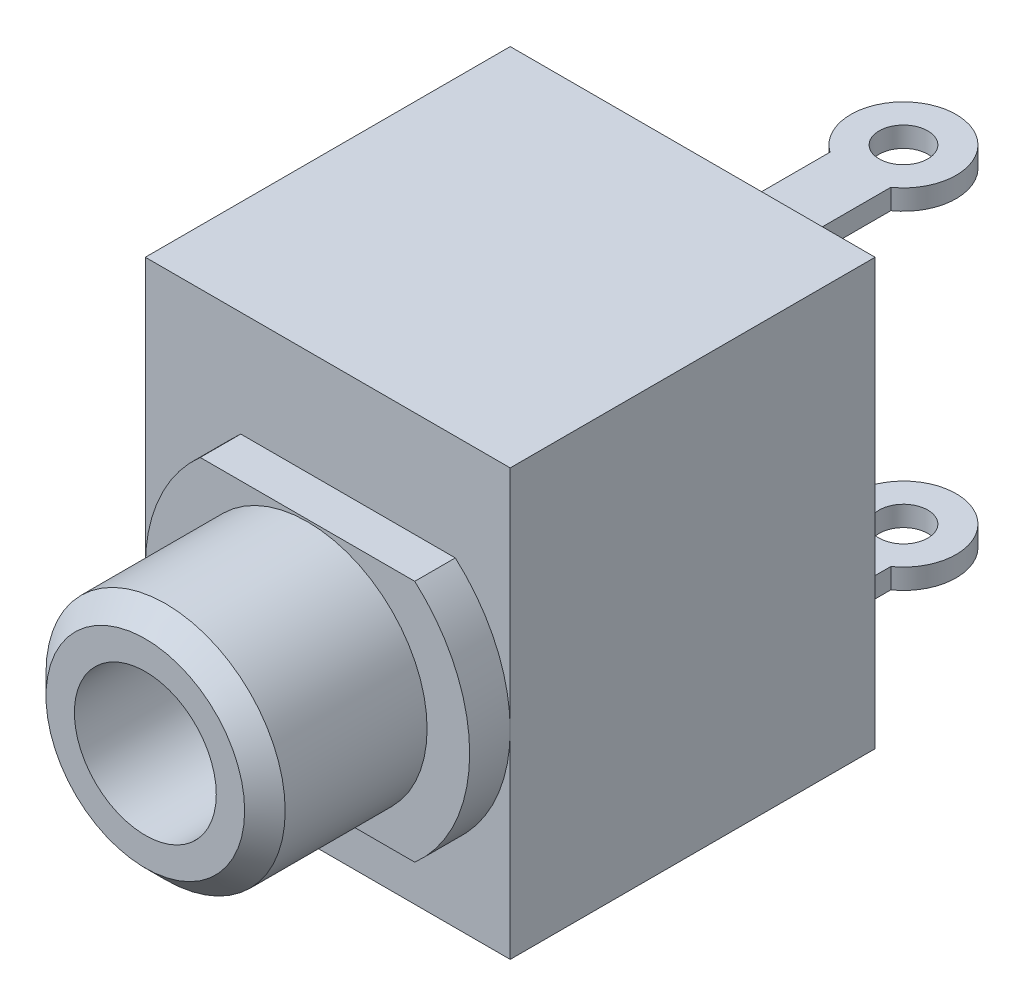
SolidWorks part; units mm, degrees
ref_plane "Front" through (0, 0, 0) normal (0, 0, 1) x (1, 0, 0)
ref_plane "Top" through (0, 0, 0) normal (0, 1, 0) x (1, 0, 0)
ref_plane "Right" through (0, 0, 0) normal (1, 0, 0) x (0, 0, -1)
sketch "Sketch3" plane through (0, 0, 0) normal (0, 0, 1) x (1, 0, 0)
  line L0 (1, -3.7) -> (1, 4.4) construction
  line L1 (-5, 5.6) -> (4, 5.6)
  line L2 (-5, 5.6) -> (-5, -4.9)
  line L3 (-5, -4.9) -> (4, -4.9)
  line L4 (4, 5.6) -> (4, -4.9)
  line L5 (0.25, -3.45) -> (1.75, -3.45)
  line L6 (0.25, -3.45) -> (0.25, -3.95)
  line L7 (0.25, -3.95) -> (1.75, -3.95)
  line L8 (1.75, -3.45) -> (1.75, -3.95)
  line L9 (0.25, -3.45) -> (1.75, -3.95) construction
  line L10 (0.25, -3.95) -> (1.75, -3.45) construction
  line L11 (-4.05, -0.65) -> (-3.55, -0.65)
  line L12 (-4.05, -0.65) -> (-4.05, -2.15)
  line L13 (-4.05, -2.15) -> (-3.55, -2.15)
  line L14 (-3.55, -0.65) -> (-3.55, -2.15)
  line L15 (-4.05, -0.65) -> (-3.55, -2.15) construction
  line L16 (-4.05, -2.15) -> (-3.55, -0.65) construction
  line L17 (0.25, 4.65) -> (1.75, 4.65)
  line L18 (0.25, 4.65) -> (0.25, 4.15)
  line L19 (0.25, 4.15) -> (1.75, 4.15)
  line L20 (1.75, 4.65) -> (1.75, 4.15)
  line L21 (0.25, 4.65) -> (1.75, 4.15) construction
  line L22 (0.25, 4.15) -> (1.75, 4.65) construction
  point P4 (1, -3.7)
  point P10 (-3.8, -1.4)
  point P15 (1, 4.4)
  dimension "D1" = 9
  dimension "D2" = 10.5
  dimension "D3" = 4
  dimension "D4" = 4.9
  dimension "D5" = 0.5
  dimension "D6" = 1.5
  dimension "D7" = 1
  dimension "D8" = 3.7
  dimension "D9" = 4.4
  dimension "D10" = 3.8
  dimension "D11" = 1.4
extrude "Boss-Extrude1" add sketch "Sketch3" along normal blind 9 contours L20 L17 L18 L19 | L14 L11 L12 L13 | L8 L5 L6 L7 | L4 L1 L2 L3 L5 L8 L7 L6 L11 L14 L13 L12 L17 L20 L19 L18 region at (-0.4976, 0.3642, 0) region at (1, -3.7, 0) region at (-3.8, -1.4, 0) region at (1, 4.4, 0)
sketch "Sketch5" plane through (0, 0, 9) normal (0, 0, 1) x (1, 0, 0)
  line L0 (4, 5.6) -> (4, -4.9) construction
  line L1 (-4, -3) -> (4, -3)
  line L2 (-4, -3) -> (-4, 3)
  line L3 (-4, 3) -> (4, 3)
  line L4 (4, -3) -> (4, 3)
  line L5 (-4, -3) -> (4, 3) construction
  line L6 (-4, 3) -> (4, -3) construction
  circle A0 centre (0, 0) radius 1.75
  circle A1 centre (0, 0) radius 2.95
  circle A2 centre (0, 0) radius 4
  dimension "D2" = 5.9
  dimension "D3" = 3.5
  dimension "D1" = 6
extrude "Boss-Extrude4" add sketch "Sketch5" along normal blind 1 contours L3 A2 L1 A1 region at (-3.5546, -1.6046, 9)
extrude "Boss-Extrude5" add sketch "Sketch5<3>" along normal blind 5 contours A1 A0 region at (-2.8666, 0, 9)
sketch "Sketch5<3>" plane through (0, 0, 9) normal (0, 0, 1) x (1, 0, 0) same geometry as "Sketch5"
extrude "Boss-Extrude6" add sketch "Sketch3<3>" against normal blind 3.7 contours L8 L5 L6 L7 | L14 L11 L12 L13 | L20 L17 L18 L19 region at (1, -3.7, 0) region at (-3.8, -1.4, 0) region at (1, 4.4, 0)
sketch "Sketch3<3>" plane through (0, 0, 0) normal (0, 0, 1) x (1, 0, 0) same geometry as "Sketch3"
sketch "Sketch6" plane through (0, -3.95, 0) normal (0, -1, 0) x (1, 0, 0)
  line L0 (0.25, -3.7) -> (1.75, -3.7) construction
  circle A0 centre (1, -3.7) radius 0.6
  circle A1 centre (1, -3.7) radius 1.3
  line M5 (0.25, -3.7) -> (1.75, -3.7)
  dimension "D1" = 1.2
  dimension "D2" = 2.6
extrude "Boss-Extrude7" add sketch "Sketch6" against normal up to surface (0.5 mm away) up to face at (1, -3.45, -1.85)
extrude "Cut-Extrude1" cut sketch "Sketch6<2>" against normal blind 3.7 contours A0 M5 region at (1, -3.95, -3.4454)
sketch "Sketch6<2>" plane through (0, -3.95, 0) normal (0, -1, 0) x (1, 0, 0) same geometry as "Sketch6"
sketch "Sketch7" plane through (0, 4.15, 0) normal (0, -1, 0) x (1, 0, 0)
  circle A1 centre (1, -3.7) radius 1.3
  circle A2 centre (1, -3.7) radius 1.3
  circle A3 centre (1, -3.7) radius 0.6
  circle A4 centre (1, -3.7) radius 0.6
  line M5 (0.25, -3.7) -> (1.75, -3.7)
  dimension "D1" = 0
  dimension "D2" = 0
extrude "Cut-Extrude2" cut sketch "Sketch7" against normal blind 3.7 contours A4 M5 region at (1, 4.15, -3.4454)
extrude "Boss-Extrude8" add sketch "Sketch7<3>" against normal up to surface (0.5 mm away) up to face at (1, 4.65, -2.3667)
sketch "Sketch7<3>" plane through (0, 4.15, 0) normal (0, -1, 0) x (1, 0, 0) same geometry as "Sketch7"
sketch "Sketch8" plane through (-4.05, 0, 0) normal (-1, 0, 0) x (0, 0, 1)
  line L0 (-3.7, -0.65) -> (-3.7, -2.15) construction
  circle A0 centre (-3.7, -1.4) radius 0.6
  circle A1 centre (-3.7, -1.4) radius 1.3
  line M5 (-3.7, -0.65) -> (-3.7, -2.15)
  dimension "D1" = 2.6
  dimension "D2" = 1.2
extrude "Cut-Extrude3" cut sketch "Sketch8" against normal blind 3.7 contours A0 M5 region at (-4.05, -1.4, -3.4454)
extrude "Boss-Extrude9" add sketch "Sketch8<3>" against normal up to surface (0.5 mm away) up to face at (-3.55, -1.4, -2.3667)
sketch "Sketch8<3>" plane through (-4.05, 0, 0) normal (-1, 0, 0) x (0, 0, 1) same geometry as "Sketch8"
chamfer "Chamfer1" distance 0.5 angle 45 1 edges at (2.95, 0, 14)
